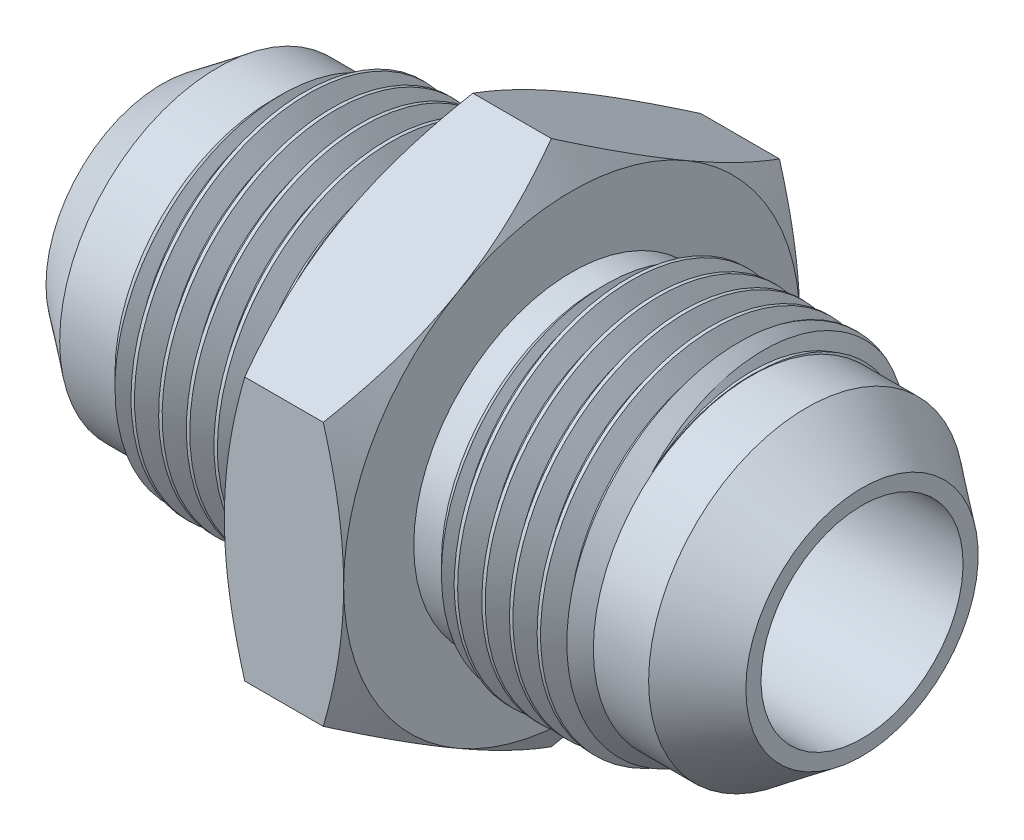
SolidWorks part; units mm, degrees
note: '?' marks a value the reader was unsure of.
ref_plane "Front" through (0, 0, 0) normal (0, 0, 1) x (1, 0, 0)
ref_plane "Top" through (0, 0, 0) normal (0, 1, 0) x (1, 0, 0)
ref_plane "Right" through (0, 0, 0) normal (1, 0, 0) x (0, 0, -1)
sketch "Sketch6" plane through (0, 0, 0) normal (0, 0, 1) x (1, 0, 0)
  line L1 (26.7891, 13.4937) -> (26.7891, -13.4937) construction
  line L2 (-26.7891, 0) -> (26.7891, 0)
  line L4 (-26.7891, 0) -> (-26.7891, 13.4937)
  line L5 (-26.7891, 13.4937) -> (26.7891, 13.4937)
  line L6 (26.7891, 0) -> (26.7891, 13.4937)
  point P4 (4.5641, 0)
  point P6 (-4.5641, 0)
  dimension "Straight Dia" = 26.9875
  dimension "Length" = 53.5781
  dimension "L1" = 22.225
  dimension "D1" = 22.225
revolve "Revolve3" add sketch "Sketch6" angle 360 about L2
sketch "Sketch14" plane through (-26.7891, 0, 0) normal (-1, 0, 0) x (0, 0, 1)
  circle A1 centre (0, 0) radius 13.4937
  circle A2 centre (0, 0) radius 13.4938
  dimension "D1" = 0
curve "Helix/Spiral1" pitch 2.1167 height 24.3417 turns 11.5 parameters "Pitch"=2.1167
sketch "Sketch15" plane through (0, 0, 0) normal (0, 0, 1) x (1, 0, 0)
  line L0 (-28.6411, 13.4937) -> (-26.7891, 13.4937)
  line L1 (-26.7891, 13.4937) -> (-27.5828, 12.1189)
  line L2 (-27.5828, 12.1189) -> (-27.8474, 12.1189)
  line L3 (-27.8474, 12.1189) -> (-28.6411, 13.4937)
  line L4 (-27.7151, 12.1189) -> (-27.7151, 13.4938) construction
  line L5 (-28.2443, 12.8063) -> (-27.1859, 12.8063) construction
  dimension "D1" = 60
  dimension "D2" = 0.2646
  dimension "D3" = 1.0583
sweep "Cut-Sweep1" cut profiles "Sketch15" path "Helix/Spiral1" align with end faces yes
sketch "Sketch16" plane through (0, 0, 0) normal (1, 0, 0) x (0, 0, -1)
  line L0 (-13.4937, 0) -> (13.4937, 0) construction
  circle A0 centre (0, 0) radius 13.4937 construction
ref_axis "Axis1" through (0, 0, 13.4937) along (0, 0, -1)?
pattern_circular "CirPattern1" count 2 every 180 about axis through (0, 0, 13.4937) along (0, 0, -1) of "Cut-Sweep1"
ref_plane "Plane1" through (-4.5641, 0, 0) normal (1, 0, 0) x (0, 0, -1)
sketch "Sketch12" plane through (-4.5641, 0, 0) normal (1, 0, 0) x (0, 0, -1)
  line L1 (0, 20.164) -> (-17.4625, 10.082)
  line L2 (-17.4625, 10.082) -> (-17.4625, -10.082)
  line L3 (-17.4625, -10.082) -> (0, -20.164)
  line L4 (0, -20.164) -> (17.4625, -10.082)
  line L5 (17.4625, -10.082) -> (17.4625, 10.082)
  line L6 (17.4625, 10.082) -> (0, 20.164)
  circle A0 centre (0, 0) radius 17.4625 construction
  dimension "Hex" = 34.925
extrude "Extrude1" add sketch "Sketch12" along normal up to vertex (9.1281 mm away) up to point (4.5641, 0, 0)
sketch "Sketch7" plane through (0, 0, 0) normal (0, 0, 1) x (1, 0, 0)
  line L0 (-26.7891, 0) -> (-26.7891, 7.7343)
  line L2 (-26.7891, 7.7343) -> (26.7891, 7.7343)
  line L4 (26.7891, 0) -> (26.7891, 13.4937) construction
  line L11 (26.7891, 7.7343) -> (26.7891, 0)
  line L12 (26.7891, 0) -> (-26.7891, 0)
  line L13 (-26.7891, 7.7343) -> (-26.7891, -7.7343) construction
  dimension "ID" = 15.4686
sketch "Sketch10" plane through (0, 0, 0) normal (0, 0, 1) x (1, 0, 0)
  line L0 (-26.7891, 13.4937) -> (26.7891, 13.4937) construction
  line L1 (-15.6646, -13.4938) -> (-15.6646, 13.4937) construction
  line L2 (-26.7891, 0) -> (-26.7891, 13.4937) construction
  line L3 (-8.0809, 13.4937) -> (-6.6807, 12.0935)
  line L4 (-28.6411, 13.4937) -> (-26.7891, 13.4937) construction
  line L5 (0, 0) -> (-26.7891, 0) construction
  line L6 (8.0809, 13.4937) -> (4.5641, 13.4937)
  line L8 (-6.6807, 12.0935) -> (-4.5641, 12.0935)
  line L9 (4.5641, 12.0935) -> (4.5641, 13.4937)
  line L11 (0, 0) -> (0, 20.164) construction
  line L12 (4.5641, 20.164) -> (-4.5641, 20.164) construction
  line L13 (-26.7891, 8.8944) -> (-26.7891, 13.4937)
  line L14 (-22.5437, 12.0935) -> (-26.7891, 8.8944)
  line L15 (-18.3104, 12.0935) -> (-22.5437, 12.0935)
  line L16 (-16.9102, 13.4937) -> (-18.3104, 12.0935)
  line L17 (-26.7891, 13.4937) -> (-16.9102, 13.4937)
  line L18 (-4.5641, 12.0935) -> (-4.5641, 13.4937)
  line L19 (-8.0809, 13.4937) -> (-4.5641, 13.4937)
  line L20 (-4.5641, -17.4625) -> (-4.5641, 17.4625) construction
  line L21 (26.7891, 13.4937) -> (16.9102, 13.4937)
  line L22 (16.9102, 13.4937) -> (18.3104, 12.0935)
  line L23 (18.3104, 12.0935) -> (22.5437, 12.0935)
  line L24 (22.5437, 12.0935) -> (26.7891, 8.8944)
  line L25 (26.7891, 8.8944) -> (26.7891, 13.4937)
  line L26 (6.6807, 12.0935) -> (4.5641, 12.0935)
  line L27 (8.0809, 13.4937) -> (6.6807, 12.0935)
  point P9 (-15.6646, -13.4938)
  point P24 (-15.6646, 0)
  dimension "D3" = 4.2333
  dimension "D4" = 37
  dimension "D5" = 2.1167
  dimension "D6" = 45
  dimension "D1" = 17.7889
  dimension "D7" = 45
  dimension "D8" = 2.6458
revolve "Cut-Revolve6" cut sketch "Sketch10" angle 360 about L2
revolve "Cut-Revolve5" cut sketch "Sketch7" angle 360 about L12
sketch "Sketch13" plane through (0, 0, 0) normal (0, 0, 1) x (1, 0, 0)
  line L0 (-4.5641, 20.164) -> (-4.5641, 17.4625)
  line L1 (-4.5641, 10.082) -> (-4.5641, 20.164) construction
  line L2 (-4.5641, 17.4625) -> (-3.0044, 20.164)
  line L3 (-3.0044, 20.164) -> (-4.5641, 20.164)
  line L4 (3.0044, 20.164) -> (4.5641, 17.4625)
  line L5 (4.5641, 20.164) -> (4.5641, 10.082) construction
  line L6 (4.5641, 17.4625) -> (4.5641, 20.164)
  line L7 (4.5641, 20.164) -> (3.0044, 20.164)
  dimension "D2" = 30
revolve "Cut-Revolve7" cut sketch "Sketch13" angle 360 about L2
equation "\"D3@Helix/Spiral1\" = \"L1@Sketch6\"+\"Pitch@Helix/Spiral1\""
equation "\"D2@Sketch15\" = \"Pitch@Helix/Spiral1\"*.125"
equation "\"D3@Sketch15\" = \"Pitch@Helix/Spiral1\"*.5"
equation "\"D3@Sketch10\" = \"Pitch@Helix/Spiral1\"*2"
equation "\"D5@Sketch10\" = \"Pitch@Helix/Spiral1\""
equation "\"D1@Sketch10\" = \"ID@Sketch7\"*1.15"
equation "\"D1@Sketch6\" = \"L1@Sketch6\""
equation "\"D8@Sketch10\" = \"Pitch@Helix/Spiral1\"*1.25"
